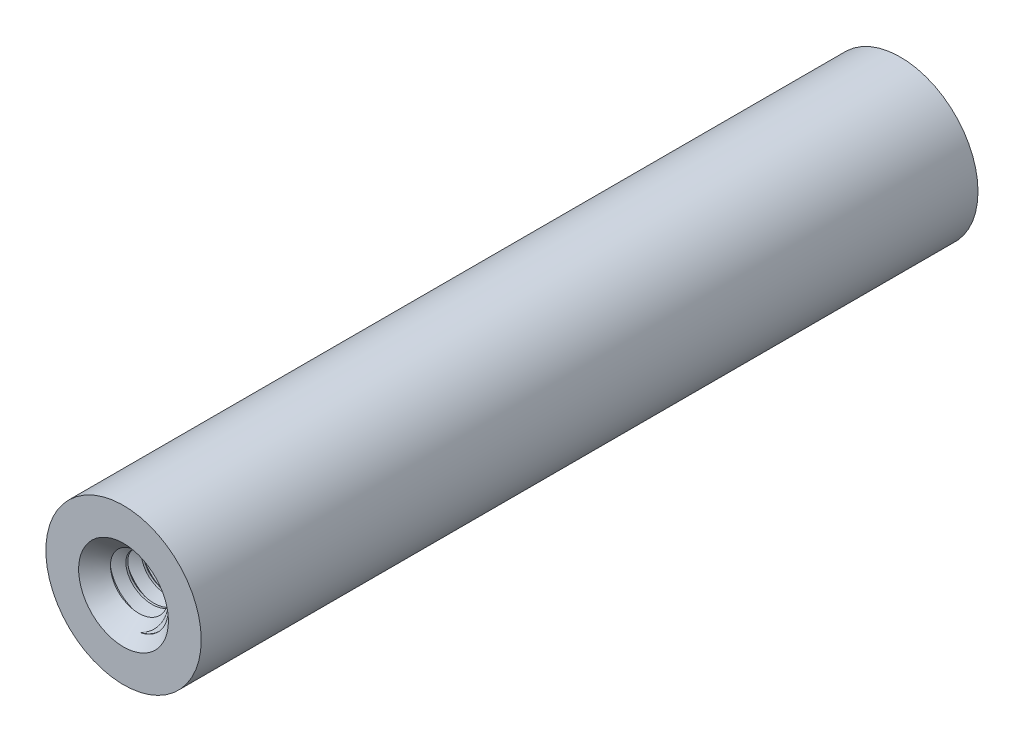
SolidWorks part; units mm, degrees
ref_plane "Front Plane" through (0, 0, 0) normal (0, 0, 1) x (1, 0, 0)
ref_plane "Top Plane" through (0, 0, 0) normal (0, 1, 0) x (1, 0, 0)
ref_plane "Right Plane" through (0, 0, 0) normal (1, 0, 0) x (0, 0, -1)
sketch "Sketch1" plane through (0, 0, 0) normal (1, 0, 0) x (0, 0, -1)
  line L0 (-15.875, 0) -> (15.875, 0) construction
  line L1 (0, 3.175) -> (0, -3.175) construction
  line L2 (-15.875, 1.4224) -> (-15.875, -1.4224) construction
  line L3 (-15.875, 1.4224) -> (-15.24, 1.4224) construction
  line L4 (-9.525, 3.175) -> (-9.525, -3.175) construction
  line L5 (9.525, 3.175) -> (9.525, -3.175) construction
  point P2 (9.525, 0)
  point P3 (-9.525, 0)
  point P13 (-9.525, 0)
  point P16 (9.525, 0)
  point P17 (-15.875, -1.4224)
  dimension "Length" = 31.75
  dimension "Min Thread Length" = 6.35
  dimension "D1" = 6.35
  dimension "Thread Dia" = 2.8448
  dimension "OD" = 6.35
  dimension "Pitch" = 0.635
sketch "Sketch2" plane through (0, 0, 0) normal (0, 0, 1) x (1, 0, 0)
  circle A1 centre (0, 0) radius 1.4224
  circle A2 centre (0, 0) radius 3.175
extrude "Extrude1" add sketch "Sketch2" along normal up to vertex (15.875 mm away) and the other way up to vertex (15.875 mm away) up to point (0, 0, 15.875) other way up to point (0, 0, -15.875)
sketch "Sketch9" plane through (0, 0, 0) normal (1, 0, 0) x (0, 0, -1)
  line L0 (-15.875, 1.4224) -> (-15.24, 1.4224) construction
  line L1 (-9.525, 1.4224) -> (9.525, 1.4224)
  line L2 (-9.525, 1.4224) -> (-9.525, 0)
  line L3 (-9.525, 0) -> (9.525, 0)
  line L4 (9.525, 1.4224) -> (9.525, 0)
  line L7 (-15.875, 0) -> (15.875, 0) construction
revolve "Revolve" add sketch "Sketch9" angle 360 about L0
chamfer "Chamfer1" distance 0.4127 angle 45 2 edges at (1.4224, 0, 15.875) (1.4224, 0, -15.875)
sketch "Sketch11" plane through (0, 0, -15.875) normal (0, 0, -1) x (-1, 0, 0)
  circle A0 centre (0, 0) radius 1.4224 construction
  circle A1 centre (0, 0) radius 1.4224
curve "Helix/Spiral1" pitch 0.635 height 7.62 radius 1.4224 centre (0, 0, -15.875) axis (0, 0, 1) start towards (0, 1, 0) parameters "Pitch"=0.635
sketch "Sketch12" plane through (0, 0, 0) normal (1, 0, 0) x (0, 0, -1)
  line L0 (15.8353, 1.4911) -> (16.1528, 0.9412) construction
  line L1 (16.1528, 0.9412) -> (16.4703, 1.4911) construction
  line L2 (16.1131, 1.01) -> (16.1925, 1.01) construction
  line L3 (16.1528, 1.01) -> (16.1528, 0.9412) construction
  line L4 (15.875, 1.4224) -> (16.4306, 1.4224) construction
  line L5 (16.4703, 1.4911) -> (15.8353, 1.4911) construction
  line L7 (16.1528, 1.4224) -> (16.1528, 1.4911) construction
  line L8 (15.8552, 1.4568) -> (16.4505, 1.4568) construction
  line L9 (16.1925, 1.01) -> (16.1131, 1.01)
  line L10 (16.1131, 1.01) -> (15.8552, 1.4568)
  line L11 (15.8552, 1.4568) -> (16.4505, 1.4568)
  line L12 (16.4505, 1.4568) -> (16.1925, 1.01)
  line L13 (15.875, 3.175) -> (15.875, 1.8351)
  line L14 (15.875, -1.8351) -> (15.875, -3.175)
  line L15 (15.875, -1.8351) -> (15.875, -3.175) construction
  line L16 (15.875, 3.175) -> (15.875, 1.8351) construction
  line L17 (15.4623, -1.4224) -> (9.525, -1.4224)
  line L18 (9.525, 1.4224) -> (15.4623, 1.4224)
  line L19 (9.525, 1.4224) -> (15.4623, 1.4224) construction
  line L20 (15.4623, -1.4224) -> (9.525, -1.4224) construction
  point P14 (16.1528, 1.4568)
  dimension "D2" = 0.635
  dimension "D1" = 60
  dimension "D3" = 0.0794
sweep "Sweep1" add profiles "Sketch12" path "Helix/Spiral1"
sketch "Sketch13" plane through (0, 0, -15.875) normal (0, 0, -1) x (-1, 0, 0)
  circle A0 centre (0, 0) radius 1.8351 construction
  circle A1 centre (0, 0) radius 1.8351
extrude "Cut-Extrude3" cut sketch "Sketch13" against normal up to surface and the other way through all up to face at (1.8351, 0, -15.875)
mirror "Mirror1" about plane through (0, 0, 0) normal (0, 0, 1) of "Sweep1"
sketch "Sketch14" plane through (0, 0, 15.875) normal (0, 0, 1) x (1, 0, 0)
  circle A0 centre (0, 0) radius 1.8352 construction
  circle A1 centre (0, 0) radius 1.8352
extrude "Cut-Extrude2" cut sketch "Sketch14" against normal up to surface and the other way through all up to face at (1.8352, 0, 15.875)
sketch "Sketch7" plane through (0, 0, -15.875) normal (0, 0, -1) x (-1, 0, 0)
  circle A2 centre (0, 0) radius 1.4732
  circle A3 centre (0, 0) radius 1.4732
  dimension "D1" = 0.0508
equation "\"D1@Sketch1\" = \"Min Thread Length@Sketch1\""
equation "\"D3@Helix/Spiral1\" = \"Min Thread Length@Sketch1\" + \"Pitch@Sketch1\" * 2"
equation "\"D2@Sketch12\"=\"Pitch@Sketch1\""
equation "\"Pitch@Helix/Spiral1\"=\"Pitch@Sketch1\""
equation "\"D3@Sketch12\"=\"D2@Sketch12\"/8"
equation "\"D1@Chamfer1\"=\"Pitch@Sketch1\"*.65"
